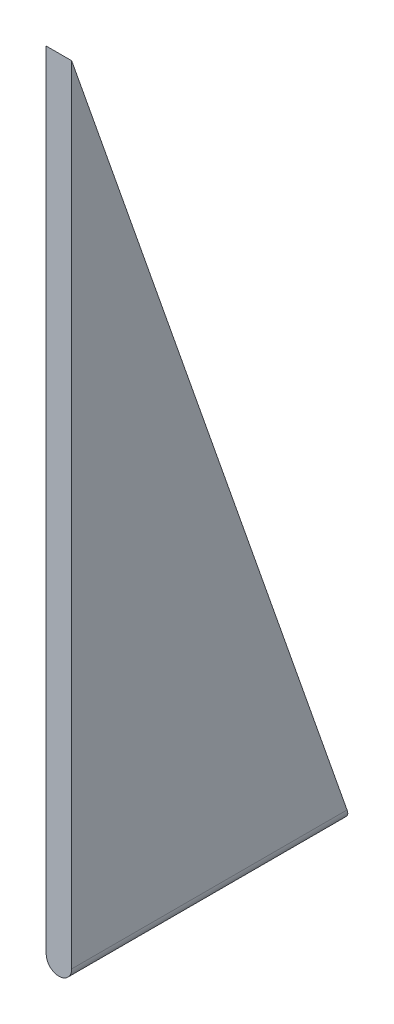
SolidWorks part; units mm, degrees
ref_plane "Front Plane" through (0, 0, 0) normal (0, 0, 1) x (1, 0, 0)
ref_plane "Top Plane" through (0, 0, 0) normal (0, 1, 0) x (1, 0, 0)
ref_plane "Right Plane" through (0, 0, 0) normal (1, 0, 0) x (0, 0, -1)
sketch "Sketch2" plane through (0, 0, 0) normal (1, 0, 0) x (0, 0, -1)
  line L0 (0, -41.2985) -> (0, 58.46)
  line L1 (0, 58.46) -> (34.925, -41.2985)
  line L3 (0, 0) -> (0, 103.1552) construction
  line L4 (0, -41.2985) -> (34.925, -41.2985)
  dimension "D1" = 99.7585
  dimension "D2" = 34.925
extrude "Boss-Extrude1" add sketch "Sketch2" along normal blind 3.175
fillet "Fillet2" 2 edges at (0, -41.2985, -17.4625) (3.175, -41.2985, -17.4625) type full round first side face at (0, -8.0456, -11.6417) second side face at (3.175, -8.0456, -11.6417) middle face at (1.5875, -41.2985, -17.4625)
